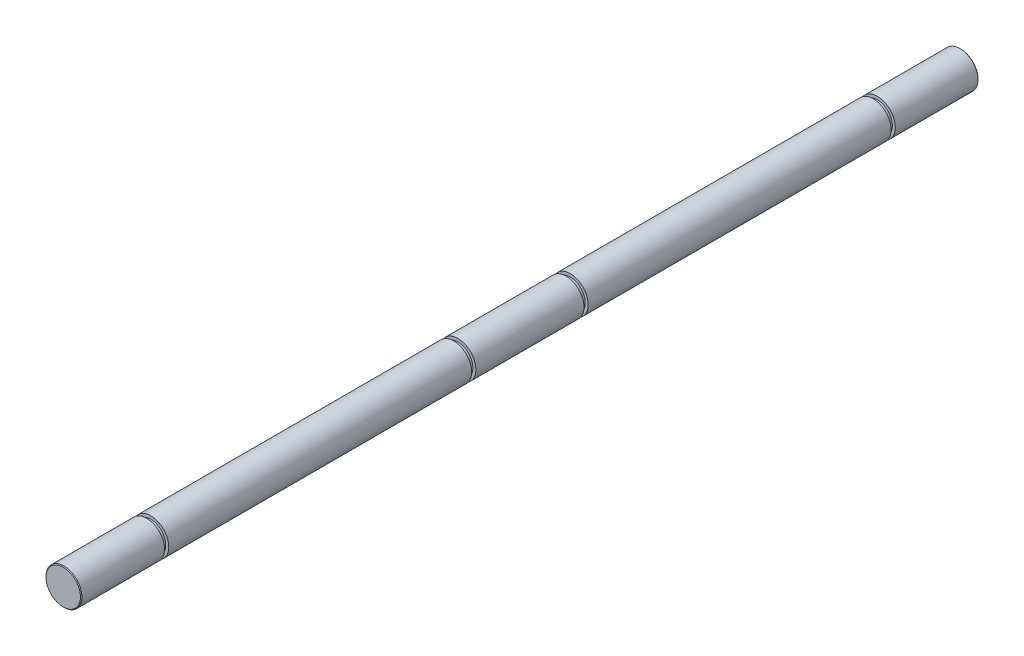
SolidWorks part; units mm, degrees
material "Alloy Steel (SS)"
ref_plane "Front Plane" through (0, 0, 0) normal (0, 0, 1) x (1, 0, 0)
ref_plane "Top Plane" through (0, 0, 0) normal (0, 1, 0) x (1, 0, 0)
ref_plane "Right Plane" through (0, 0, 0) normal (1, 0, 0) x (0, 0, -1)
sketch "Sketch1" plane through (0, 0, 0) normal (1, 0, 0) x (0, 0, -1)
  line L0 (-75, 0) -> (75, 0) construction
  line L1 (0, -3) -> (0, 3) construction
  point P4 (0, 0)
  point P8 (0, 0)
sketch "Sketch2" plane through (0, 0, 0) normal (0, 0, 1) x (1, 0, 0)
  circle A0 centre (0, 0) radius 3
extrude "Boss-Extrude1" add sketch "Sketch2" along normal up to vertex (75 mm away) and the other way up to vertex (75 mm away) up to point (0, 0, 75) other way up to point (0, 0, -75)
chamfer "Chamfer1" distance 0.12 angle 45 2 edges at (3, 0, -75) (3, 0, 75)
sketch "Sketch3" plane through (0, 0, 75) normal (0, 0, 1) x (1, 0, 0)
  circle A0 centre (0, 0) radius 3
  circle A1 centre (0, 0) radius 2.5
  circle A2 centre (0, 0) radius 3 construction
  dimension "D1" = 0.5
extrude "Cut-Extrude1" cut sketch "Sketch3" against normal blind 0.7 from offset 13.9361 offset against normal yes
ref_plane "Plane1" through (0, 0, 0) normal (0, 0, 1) x (1, 0, 0)
mirror "Mirror1" about plane through (0, 0, 0) normal (0, 0, 1) of "Cut-Extrude1"
extrude "Cut-Extrude2" cut sketch "Sketch3<2>" against normal blind 0.7 from offset 65.26 offset against normal yes
sketch "Sketch3<2>" plane through (0, 0, 75) normal (0, 0, 1) x (1, 0, 0) same geometry as "Sketch3"
mirror "Mirror2" about plane through (0, 0, 0) normal (0, 0, 1) of "Cut-Extrude2"
equation "\"D1@Chamfer1\"=\"Diameter@Sketch1\"*.02"
